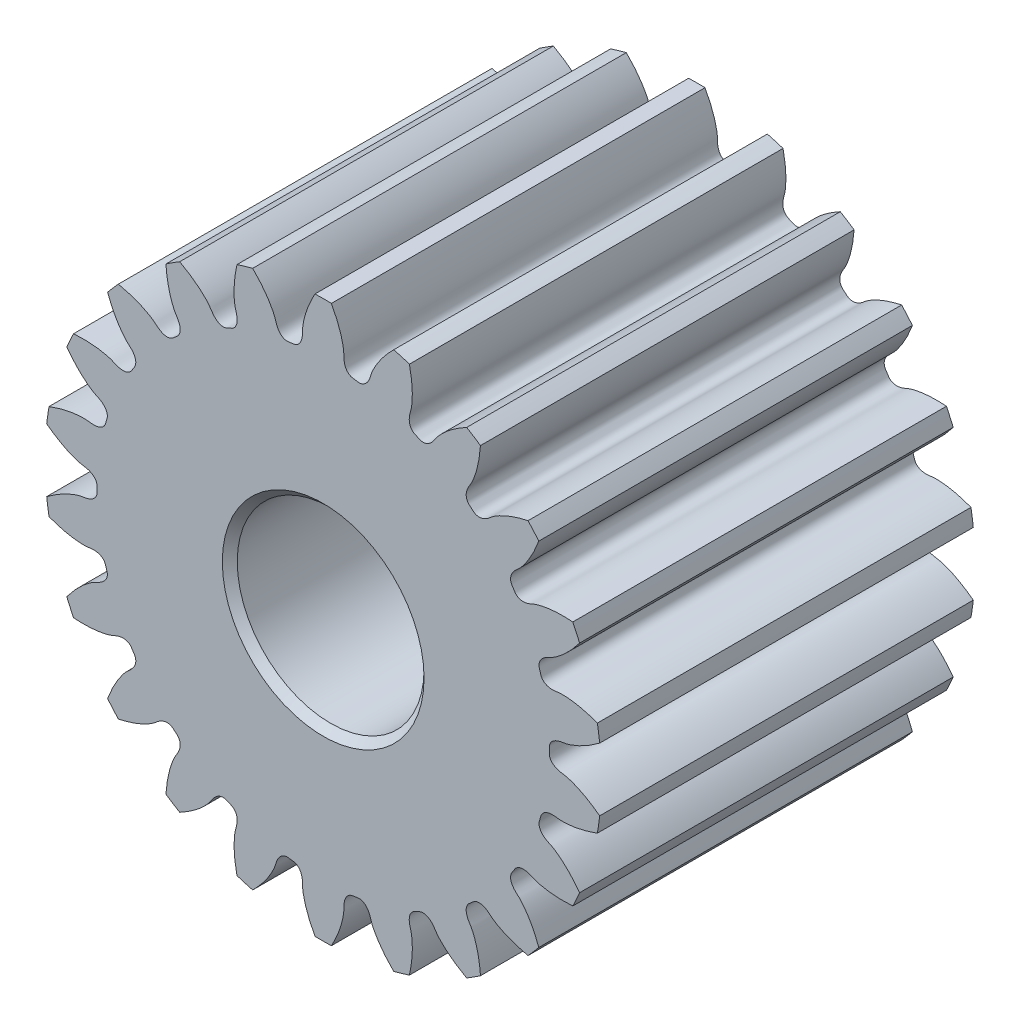
SolidWorks part; units mm, degrees
ref_plane "Front Plane" through (0, 0, 0) normal (0, 0, 1) x (1, 0, 0)
ref_plane "Top Plane" through (0, 0, 0) normal (0, 1, 0) x (1, 0, 0)
ref_plane "Right Plane" through (0, 0, 0) normal (1, 0, 0) x (0, 0, -1)
ref_axis "Axis1" through (0, 0, 55) along (0, 0, -1)
sketch "SketchRevolveSun_Fixed01" plane through (0, 0, 0) normal (1, 0, 0) x (0, 0, -1)
  line L0 (0, 0) -> (25.4, 0) construction
  line L1 (-6.35, 0) -> (-6.35, 9.4588)
  line L2 (-6.35, 9.4588) -> (6.35, 9.4588)
  line L3 (6.35, 9.4588) -> (6.35, 0)
  line L4 (6.35, 0) -> (-6.35, 0)
  dimension "Side1" = 6.35
  dimension "OutsideRadius" = 9.4588
  dimension "Side2" = 6.35
revolve "Sun_Fixed01" add sketch "SketchRevolveSun_Fixed01" angle 360 about L0
sketch "SketchToothSun_Fixed01" plane through (0, 0, 0) normal (0, 0, 1) x (1, 0, 0)
  arc A0 (9.4346, 1.0979) -> (9.4346, -1.0979) centre (0, 0) cw
  spline S0 degree 3 poles (9.4346, -1.0979) (9.3611, -1.0415) (9.2516, -0.962) (9.1049, -0.8657) (9.0021, -0.8025) (8.9038, -0.746) (8.8103, -0.696) (8.7219, -0.652) (8.6388, -0.6138) (8.5614, -0.5809) (8.4899, -0.553) (8.4244, -0.5297) (8.3653, -0.5106) (8.3126, -0.4954) (8.2666, -0.4835) (8.2273, -0.4746) (8.1676, -0.4628) (8.1129, -0.4572) (8.0626, -0.4469) (8.0413, -0.4421) (8.0203, -0.4368) (7.9998, -0.4311) (7.9797, -0.4248) (7.96, -0.4181) (7.9407, -0.4108) (7.9217, -0.4029) (7.903, -0.3943) (7.8845, -0.3851) (7.8664, -0.375) (7.8485, -0.364) (7.8308, -0.3521) (7.8134, -0.339) (7.7962, -0.3245) (7.7793, -0.3086) (7.763, -0.291) (7.7472, -0.2714) (7.7323, -0.2498) (7.7186, -0.2259) (7.7066, -0.1997) (7.6967, -0.1715) (7.6895, -0.1413) (7.6857, -0.1119) (7.684, -0.0647) (7.6863, 0) (7.684, 0.0647) (7.6857, 0.1119) (7.6895, 0.1413) (7.6967, 0.1715) (7.7066, 0.1997) (7.7186, 0.2259) (7.7323, 0.2498) (7.7472, 0.2714) (7.763, 0.291) (7.7793, 0.3086) (7.7962, 0.3245) (7.8134, 0.339) (7.8308, 0.3521) (7.8485, 0.364) (7.8664, 0.375) (7.8845, 0.3851) (7.903, 0.3943) (7.9217, 0.4029) (7.9407, 0.4108) (7.96, 0.4181) (7.9797, 0.4248) (7.9998, 0.4311) (8.0203, 0.4368) (8.0413, 0.4421) (8.0626, 0.4469) (8.1129, 0.4572) (8.1676, 0.4628) (8.2273, 0.4746) (8.2666, 0.4835) (8.3126, 0.4954) (8.3653, 0.5106) (8.4244, 0.5297) (8.4899, 0.553) (8.5614, 0.5809) (8.6388, 0.6138) (8.7219, 0.652) (8.8103, 0.696) (8.9038, 0.746) (9.0021, 0.8025) (9.1049, 0.8657) (9.2516, 0.962) (9.3611, 1.0415) (9.4346, 1.0979) knots 0 0 0 0 0.063463 0.092689 0.120245 0.146131 0.170347 0.192893 0.213769 0.232975 0.25051 0.266376 0.280572 0.293097 0.303953 0.313138 0.320653 0.345676 0.350759 0.35576 0.360686 0.365546 0.370347 0.375102 0.37982 0.384517 0.389207 0.393908 0.39864 0.403426 0.40829 0.413262 0.418372 0.423652 0.429137 0.43486 0.440848 0.447122 0.453688 0.460533 0.467623 0.474898 0.480792 0.5 0.519208 0.525102 0.532377 0.539467 0.546312 0.552878 0.559152 0.56514 0.570863 0.576348 0.581628 0.586738 0.59171 0.596574 0.60136 0.606092 0.610793 0.615483 0.62018 0.624898 0.629653 0.634454 0.639314 0.64424 0.649241 0.654324 0.679347 0.686862 0.696047 0.706903 0.719428 0.733624 0.74949 0.767025 0.786231 0.807107 0.829653 0.853869 0.879755 0.907311 0.936537 1 1 1 1
extrude "ToothExtrudeCutSun_Fixed01" cut sketch "SketchToothSun_Fixed01" against normal blind 6.35 and the other way blind 6.35
ref_axis "Axis2" through (10.4461, 0, 0) along (-1, 0, 0)
ref_plane "Plane1" through (0, 0, 0) normal (0, 0, -1) x (1, 0, 0)
pattern_circular "PatternSun_Fixed01" count 22 every 16.364 about axis through (0, 0, 55) along (0, 0, -1) of "ToothExtrudeCutSun_Fixed01"
sketch "BoreRevolveSketch" plane through (0, 0, 0) normal (1, 0, 0) x (0, 0, -1)
  line L0 (0, 0) -> (25.4, 0) construction
  line L1 (-6.35, 0) -> (6.35, 0)
  line L2 (6.35, 0) -> (6.35, 3.429)
  line L3 (6.35, 3.429) -> (6.096, 3.175)
  line L4 (6.096, 3.175) -> (-6.096, 3.175)
  line L5 (-6.096, 3.175) -> (-6.35, 3.429)
  line L6 (-6.35, 3.429) -> (-6.35, 0)
  dimension "BoreSide1" = 6.35
  dimension "TaperSide1" = 3.429
  dimension "Chamfer1X" = 0.254
  dimension "Chamfer1Y" = 0.254
  dimension "BoreSide2" = 6.35
  dimension "TaperSide2" = 3.429
revolve "BoreRevolveCut" cut sketch "BoreRevolveSketch" angle 360 about L0
sketch "AuxiliarySketchSun_Fixed01" plane through (0, 0, 0) normal (0, 0, 1) x (1, 0, 0)
  circle A0 centre (0, 0) radius 8.6706 construction
  circle A1 centre (0, 0) radius 8.1477 construction
  circle A2 centre (0, 0) radius 8.1655 construction
  circle A3 centre (0, 0) radius 9.4588 construction
  circle A4 centre (0, 0) radius 7.6853 construction
  dimension "PitchDiameter" = 17.3412
  dimension "BaseDiameter" = 16.2954
  dimension "FormDiameter" = 16.3311
  dimension "MajorDiameter" = 18.9176
  dimension "MinorDiameter" = 15.3706
